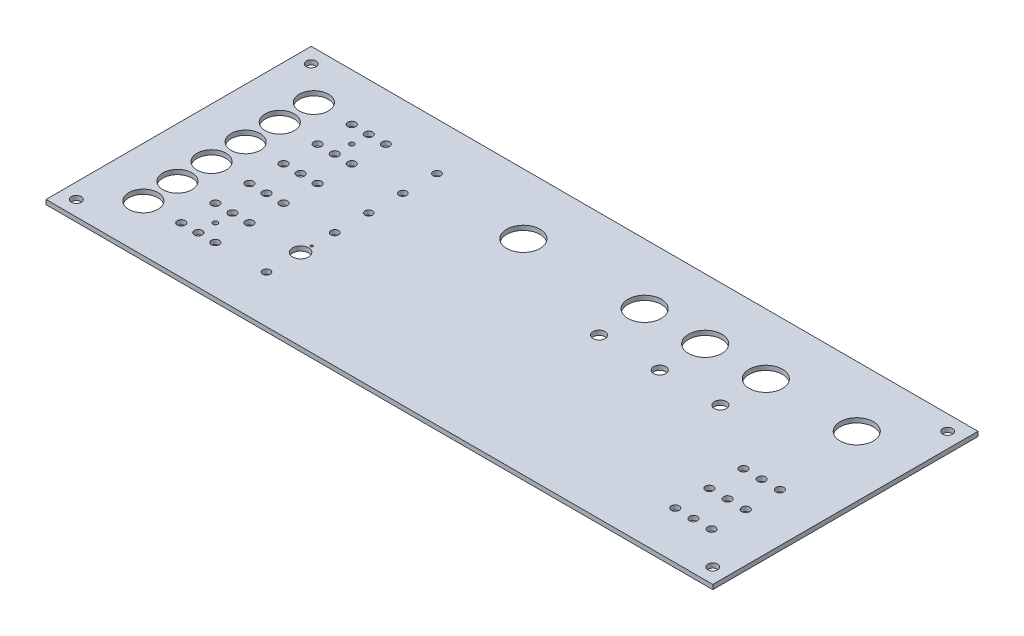
SolidWorks part; units mm, degrees
ref_plane "Front Plane" through (0, 0, 0) normal (0, 0, 1) x (1, 0, 0)
ref_plane "Top Plane" through (0, 0, 0) normal (0, 1, 0) x (1, 0, 0)
ref_plane "Right Plane" through (0, 0, 0) normal (1, 0, 0) x (0, 0, -1)
sketch "Sketch1" plane through (0, 0, 0) normal (0, 1, 0) x (1, 0, 0)
  line L0 (420, 20) -> (20, 20) construction
  line L1 (440, 175) -> (0, 175)
  line L2 (440, 175) -> (440, 0)
  line L3 (440, 0) -> (0, 0)
  line L4 (0, 175) -> (0, 0)
  line L5 (20, 155) -> (20, 20) construction
  line L6 (420, 155) -> (20, 155) construction
  line L7 (420, 155) -> (420, 20) construction
  line L8 (114.25, 20) -> (114.25, 155) construction
  line L9 (20, 143.75) -> (120, 143.75) construction
  line L10 (33, 20) -> (33, 155) construction
  line L11 (20, 121.25) -> (120, 121.25) construction
  line L12 (58, 20) -> (58, 155) construction
  line L13 (120, 98.75) -> (20, 98.75) construction
  line L14 (69.25, 20) -> (69.25, 155) construction
  line L15 (20, 76.25) -> (420, 76.25) construction
  line L16 (80.5, 20) -> (80.5, 155) construction
  line L17 (420, 53.75) -> (20, 53.75) construction
  line L18 (420, 105) -> (150, 105) construction
  line L19 (20, 31.25) -> (420, 31.25) construction
  line L20 (420, 135) -> (150, 135) construction
  line L21 (260, 135) -> (260, 105) construction
  line L22 (300, 135) -> (300, 105) construction
  line L23 (340, 135) -> (340, 105) construction
  circle A0 centre (10, 10) radius 3.25
  circle A1 centre (10, 165) radius 3.25
  circle A2 centre (430, 165) radius 3.25
  circle A3 centre (430, 10) radius 3.25
  circle A4 centre (33, 31.25) radius 9.6
  circle A5 centre (33, 53.75) radius 9.6
  circle A6 centre (33, 76.25) radius 9.6
  circle A7 centre (33, 98.75) radius 9.6
  circle A8 centre (33, 121.25) radius 9.6
  circle A9 centre (33, 143.75) radius 9.6
  circle A10 centre (33, 31.25) radius 11 construction
  circle A11 centre (33, 53.75) radius 11 construction
  circle A12 centre (58, 31.25) radius 2.6
  circle A13 centre (58, 53.75) radius 2.6
  circle A14 centre (58, 76.25) radius 2.6
  circle A15 centre (58, 98.75) radius 2.6
  circle A16 centre (58, 121.25) radius 2.6
  circle A17 centre (58, 143.75) radius 2.6
  circle A18 centre (69.25, 31.25) radius 2.6
  circle A19 centre (69.25, 53.75) radius 2.6
  circle A20 centre (69.25, 76.25) radius 2.6
  circle A21 centre (69.25, 98.75) radius 2.6
  circle A22 centre (69.25, 121.25) radius 2.6
  circle A23 centre (69.25, 143.75) radius 2.6
  circle A24 centre (80.5, 31.25) radius 2.6
  circle A25 centre (80.5, 53.75) radius 2.6
  circle A26 centre (80.5, 76.25) radius 2.6
  circle A27 centre (80.5, 98.75) radius 2.6
  circle A28 centre (80.5, 121.25) radius 2.6
  circle A29 centre (80.5, 143.75) radius 2.6
  circle A30 centre (400, 135) radius 11
  circle A31 centre (340, 135) radius 11
  circle A32 centre (300, 135) radius 11
  circle A33 centre (260, 135) radius 11
  circle A34 centre (180, 135) radius 11
  circle A35 centre (408, 31.25) radius 2.6
  circle A36 centre (396, 31.25) radius 2.6
  circle A37 centre (384, 31.25) radius 2.6
  circle A38 centre (408, 53.75) radius 2.6
  circle A39 centre (396, 53.75) radius 2.6
  circle A40 centre (384, 53.75) radius 2.6
  circle A41 centre (408, 76.25) radius 2.6
  circle A42 centre (396, 76.25) radius 2.6
  circle A43 centre (384, 76.25) radius 2.6
  circle A44 centre (114.25, 143.75) radius 2.5
  circle A45 centre (114.25, 121.25) radius 2.5
  circle A46 centre (114.25, 98.75) radius 2.5
  circle A47 centre (114.25, 76.25) radius 2.5
  circle A48 centre (114.25, 53.75) radius 5.25
  circle A49 centre (114.25, 31.25) radius 2.5
  circle A50 centre (114.25, 61.17) radius 0.8
  circle A51 centre (69.25, 132.5) radius 1.6
  circle A52 centre (69.25, 42.5) radius 1.6
  circle A53 centre (260, 105) radius 4
  circle A54 centre (300, 105) radius 4
  circle A55 centre (340, 105) radius 4
  dimension "D1" = 135
  dimension "D3" = 22.5
  dimension "D28" = 10
  dimension "D30" = 10
  dimension "D31" = 10
  dimension "D33" = 260
  dimension "D21" = 10.5
  dimension "D34" = 5.2
  dimension "D35" = 7.42
  dimension "D36" = 1.6
  dimension "D37" = 11.25
  dimension "D38" = 11.25
  dimension "D39" = 3.2
  dimension "D40" = 3.2
  dimension "D42" = 22
  dimension "D64" = 19.2
  dimension "D65" = 6.5
  dimension "D67" = 8
  dimension "D4" = 22.5
  dimension "D5" = 22.5
  dimension "D6" = 22.5
  dimension "D7" = 22.5
  dimension "D8" = 11.25
  dimension "D9" = 11.25
  dimension "D10" = 11.25
  dimension "D11" = 25
  dimension "D12" = 13
  dimension "D13" = 20
  dimension "D14" = 12
  dimension "D15" = 12
  dimension "D16" = 12
  dimension "D17" = 40
  dimension "D18" = 100
  dimension "D19" = 140
  dimension "D20" = 180
  dimension "D22" = 440
  dimension "D23" = 400
  dimension "D24" = 33.75
  dimension "D25" = 10
  dimension "D26" = 10
  dimension "D27" = 10
  dimension "D29" = 10
  dimension "D32" = 10
  dimension "D41" = 175
  dimension "D43" = 40
  dimension "D44" = 98.75
  dimension "D45" = 121.25
  dimension "D46" = 143.75
  dimension "D47" = 31.25
  dimension "D48" = 53.75
  dimension "D49" = 76.25
  dimension "D50" = 32
  dimension "D51" = 44
  dimension "D52" = 56
  dimension "D53" = 31.25
  dimension "D54" = 53.75
  dimension "D55" = 76.25
  dimension "D56" = 98.75
  dimension "D57" = 121.25
  dimension "D58" = 143.75
  dimension "D59" = 114.25
  dimension "D60" = 33
  dimension "D61" = 58
  dimension "D62" = 69.25
  dimension "D63" = 80.5
  dimension "D66" = 70
extrude "Boss-Extrude1" add sketch "Sketch1" along normal blind 3
